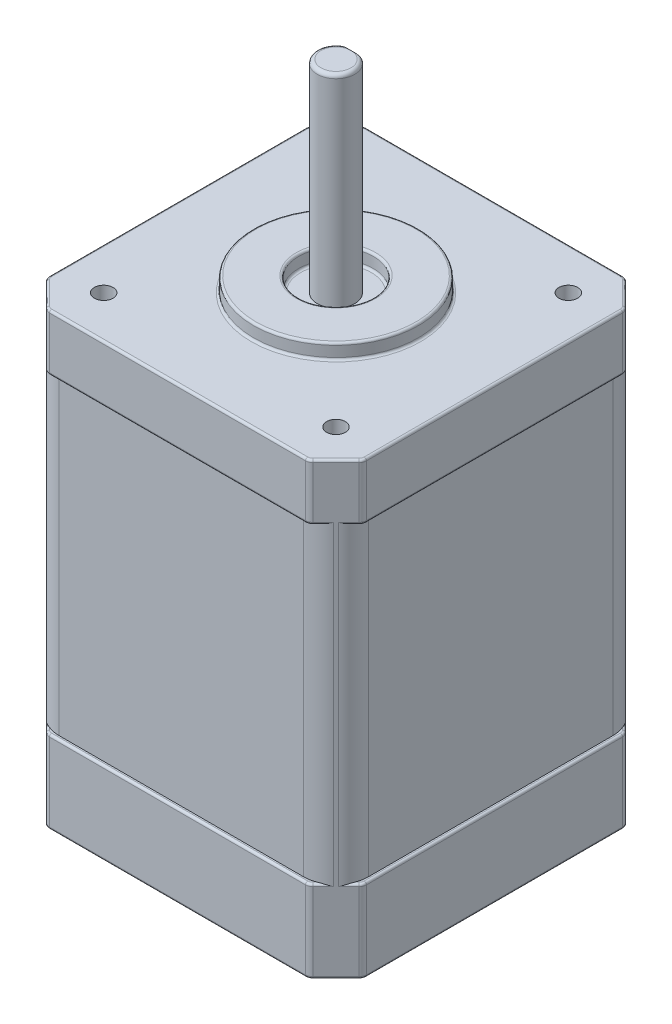
SolidWorks part; units mm, degrees
ref_plane "Front Plane" through (0, 0, 0) normal (0, 0, 1) x (1, 0, 0)
ref_plane "Top Plane" through (0, 0, 0) normal (0, 1, 0) x (1, 0, 0)
ref_plane "Right Plane" through (0, 0, 0) normal (1, 0, 0) x (0, 0, -1)
ref_plane "BottomMotorFacePlane" through (0, -60, 0) normal (0, 1, 0) x (1, 0, 0)
ref_plane "ProtrudngNubPlane" through (0, 2, 0) normal (0, 1, 0) x (1, 0, 0)
ref_plane "MotorShaftLimit" through (0, 27, 0) normal (0, 1, 0) x (1, 0, 0)
ref_plane "Front Cutout Plane" through (0, -7.5, 0) normal (0, 1, 0) x (1, 0, 0)
ref_plane "Rear Cutout Plane" through (0, -49, 0) normal (0, 1, 0) x (1, 0, 0)
ref_plane "JST Connnector Side Plane" through (-8, 0, 0) normal (1, 0, 0) x (0, 0, -1)
sketch "MasterLayoutSketch" plane through (0, 0, 0) normal (0, 1, 0) x (1, 0, 0)
  line L12 (-21.15, 21.15) -> (21.15, -21.15) construction
  line L13 (-21.15, 21.15) -> (21.15, 21.15) construction
  line L14 (-21.15, 21.15) -> (-21.15, -21.15) construction
  line L15 (-21.15, -21.15) -> (21.15, -21.15) construction
  line L17 (-21.15, -21.15) -> (21.15, 21.15) construction
  line L18 (21.15, 21.15) -> (21.15, -21.15) construction
  line L19 (-21.15, 17.5) -> (-21.15, -17.5)
  line L20 (-21.15, -17.5) -> (-17.5, -21.15)
  line L21 (-17.5, -21.15) -> (17.5, -21.15)
  line L22 (17.5, -21.15) -> (21.15, -17.5)
  line L23 (21.15, -17.5) -> (21.15, 17.5)
  line L24 (21.15, 17.5) -> (17.5, 21.15)
  line L25 (17.5, 21.15) -> (-17.5, 21.15)
  line L26 (-17.5, 21.15) -> (-21.15, 17.5)
  line L27 (-1.5, 2) -> (1.5, 2)
  line L28 (0, -2.5) -> (0, 2) construction
  circle A0 centre (0, 0) radius 11
  arc A1 (-1.5, 2) -> (1.5, 2) centre (0, 0) ccw
  point P8 (-15.5, 15.5)
  point P18 (15.5, 15.5)
  point P19 (15.5, -15.5)
  point P22 (-15.5, -15.5)
  dimension "D3" = 22
  dimension "D4" = 5
  dimension "D6" = 31
  dimension "D1" = 42.3
  dimension "D2" = 35
  dimension "D5" = 4.5
sketch "HolePositionSketch" plane through (0, 0, 0) normal (0, 1, 0) x (1, 0, 0)
  point P0 (-15.5, -15.5)
  point P2 (15.5, -15.5)
  point P4 (15.5, 15.5)
  point P6 (-15.5, 15.5)
sketch "MainBodySketch" plane through (0, 0, 0) normal (0, 1, 0) x (1, 0, 0)
  line L0 (21.15, 17.5) -> (17.5, 21.15) construction
  line L1 (21.15, -17.5) -> (21.15, 17.5) construction
  line L2 (17.5, -21.15) -> (21.15, -17.5) construction
  line L3 (-17.5, -21.15) -> (17.5, -21.15) construction
  line L4 (-21.15, -17.5) -> (-17.5, -21.15) construction
  line L5 (-21.15, 17.5) -> (-21.15, -17.5) construction
  line L6 (17.5, 21.15) -> (-17.5, 21.15) construction
  line L7 (-17.5, 21.15) -> (-21.15, 17.5) construction
  line L8 (21.15, 17.5) -> (17.5, 21.15)
  line L9 (21.15, -17.5) -> (21.15, 17.5)
  line L10 (17.5, -21.15) -> (21.15, -17.5)
  line L11 (-17.5, -21.15) -> (17.5, -21.15)
  line L12 (-21.15, -17.5) -> (-17.5, -21.15)
  line L13 (-21.15, 17.5) -> (-21.15, -17.5)
  line L14 (17.5, 21.15) -> (-17.5, 21.15)
  line L15 (-17.5, 21.15) -> (-21.15, 17.5)
extrude "MainMotorBody" add sketch "MainBodySketch" against normal up to surface (60 mm away) up to plane "BottomMotorFacePlane"
sketch "ProtrudingNubSketch" plane through (0, 0, 0) normal (0, 1, 0) x (1, 0, 0)
  circle A0 centre (0, 0) radius 11 construction
  circle A1 centre (0, 0) radius 11
  circle A2 centre (0, 0) radius 5
  dimension "D1" = 10
extrude "ProtrudingNub" add sketch "ProtrudingNubSketch" along normal up to surface (2 mm away) up to plane "ProtrudngNubPlane"
sketch "MotorShaftSketch" plane through (0, 0, 0) normal (0, 1, 0) x (1, 0, 0)
  line L0 (-1.5, 2) -> (1.5, 2) construction
  line L1 (-1.5, 2) -> (1.5, 2)
  arc A0 (-1.5, 2) -> (1.5, 2) centre (0, 0) ccw construction
  arc A1 (-1.5, 2) -> (1.5, 2) centre (0, 0) ccw
extrude "MotorShaft" add sketch "MotorShaftSketch" along normal up to surface (27 mm away) up to plane "MotorShaftLimit"
sketch "JST-PHConnectorSketch" plane through (0, -60, 0) normal (0, 1, 0) x (1, 0, 0)
  line L0 (17.5, 21.15) -> (-17.5, 21.15) construction
  line L1 (-8, 21.15) -> (8, 21.15)
  line L2 (-8, 21.15) -> (-8, 27.15)
  line L3 (-8, 27.15) -> (8, 27.15)
  line L4 (8, 21.15) -> (8, 27.15)
  line L5 (-8, 21.15) -> (8, 27.15) construction
  line L6 (-8, 27.15) -> (8, 21.15) construction
  point P0 (0, 24.15)
  dimension "D1" = 6
  dimension "D2" = 16
extrude "JST Connector" add sketch "JST-PHConnectorSketch" along normal blind 10.9
hole_wizard "M3MountingHoles" positions "Sketch8" profile "Sketch9" tap size "M3" standard "ISO"
sketch "Sketch8" plane through (0, 0, 0) normal (0, 1, 0) x (1, 0, 0)
  point P0 (-15.5, 15.5)
  point P3 (15.5, 15.5)
  point P6 (15.5, -15.5)
  point P9 (-15.5, -15.5)
sketch "Sketch9" plane through (-15.5, 0, -15.5) normal (1, 0, 0) x (0, 0, 1)
  line L0 (0, 0) -> (0, 6.7511)
  line L1 (0, 6.7511) -> (1.25, 6)
  line L2 (1.25, 6) -> (1.25, 0)
  line L5 (1.25, 0) -> (0, 0)
  line L10 (0, 6.7511) -> (-1.25, 6) construction
  line L11 (0, -6.35) -> (0, 107.95) construction
  dimension "Tap Drill Dia." = 2.5
  dimension "Tap Drill Depth" = 6
  dimension "Drill Angle" = 118
cosmetic thread "Hole Thread1" parameters "D1"=4.5, "D2"=3
cosmetic thread "Hole Thread2" parameters "D1"=4.5, "D2"=3
cosmetic thread "Hole Thread3" parameters "D1"=4.5, "D2"=3
cosmetic thread "Hole Thread4" parameters "D1"=4.5, "D2"=3
sketch "Cutout Sketch" plane through (0, -7.5, 0) normal (0, 1, 0) x (1, 0, 0)
  line L0 (21.15, 17.5) -> (17.5, 21.15) construction
  line L1 (17.5, 21.15) -> (-17.5, 21.15) construction
  line L2 (-17.5, 21.15) -> (-21.15, 17.5) construction
  line L3 (-21.15, 17.5) -> (-21.15, -17.5) construction
  line L4 (-21.15, -17.5) -> (-17.5, -21.15) construction
  line L5 (-17.5, -21.15) -> (17.5, -21.15) construction
  line L6 (17.5, -21.15) -> (21.15, -17.5) construction
  line L7 (21.15, -17.5) -> (21.15, 17.5) construction
  line L8 (21.15, 17.5) -> (20.65, 18)
  line L9 (17.5, 21.15) -> (-17.5, 21.15)
  line L10 (-17.5, 21.15) -> (-18, 20.65)
  line L11 (-21.15, 17.5) -> (-21.15, -17.5)
  line L12 (-21.15, -17.5) -> (-20.65, -18)
  line L13 (-17.5, -21.15) -> (17.5, -21.15)
  line L14 (17.5, -21.15) -> (18, -20.65)
  line L15 (21.15, -17.5) -> (21.15, 17.5)
  line L16 (-20.65, 18) -> (-20.65, -18)
  line L17 (-20.65, -20.65) -> (20.65, -20.65) construction
  line L18 (-20.65, -20.65) -> (-20.65, 20.65) construction
  line L19 (-20.65, 20.65) -> (20.65, 20.65) construction
  line L20 (20.65, -20.65) -> (20.65, 20.65) construction
  line L21 (-20.65, -20.65) -> (20.65, 20.65) construction
  line L22 (-20.65, 20.65) -> (20.65, -20.65) construction
  line L23 (-18, -20.65) -> (18, -20.65)
  line L24 (20.65, -18) -> (20.65, 18)
  line L25 (18, 20.65) -> (-18, 20.65)
  line L26 (-20.65, 18) -> (-21.15, 17.5)
  line L27 (18, 20.65) -> (17.5, 21.15)
  line L28 (20.65, -18) -> (21.15, -17.5)
  line L29 (-18, -20.65) -> (-17.5, -21.15)
  point P2 (0, 0)
  dimension "D1" = 0.5
extrude "Cutout" cut sketch "Cutout Sketch" against normal up to surface (41.5 mm away)
sketch "JST Connector Cutout" plane through (-8, 0, 0) normal (1, 0, 0) x (0, 0, -1)
  line L0 (27.15, -56) -> (21.15, -56)
  line L1 (21.15, -60) -> (27.15, -60) construction
  line L2 (21.15, -60) -> (27.15, -60) construction
  line L3 (21.15, -60) -> (21.15, -49) construction
  line L4 (21.15, -49) -> (27.15, -49) construction
  line L5 (27.15, -49) -> (27.15, -60) construction
  line L6 (21.15, -56) -> (21.15, -55.5)
  line L7 (21.15, -55.5) -> (27.15, -55.5)
  line L8 (27.15, -55.5) -> (27.15, -56)
  dimension "D1" = 11
  dimension "D2" = 0.5
  dimension "D3" = 4
extrude "JST Connector Split Cutout" cut sketch "JST Connector Cutout" along normal through all
fillet "Cosmetic Fillets" radius 4 8 edges at (18, -28.25, 20.65) (20.65, -28.25, 18) (-18, -28.25, 20.65) (-20.65, -28.25, 18) (-18, -28.25, -20.65) (-20.65, -28.25, -18) (18, -28.25, -20.65) (20.65, -28.25, -18)
fillet "Tiny Fillets" radius 1 16 edges at (-17.5, -3.75, -21.15) (-21.15, -3.75, -17.5) (-21.15, -3.75, 17.5) (-17.5, -3.75, 21.15) (17.5, -3.75, 21.15) (21.15, -3.75, 17.5) (21.15, -3.75, -17.5) (17.5, -3.75, -21.15) (17.5, -54.5, -21.15) (21.15, -54.5, -17.5) (21.15, -54.5, 17.5) (17.5, -54.5, 21.15) (-17.5, -54.5, 21.15) (-21.15, -54.5, 17.5) (-17.5, -54.5, -21.15) (-21.15, -54.5, -17.5)
fillet "Rear Block Fillets" radius 1 4 edges at (8, -58, -21.15) (-8, -58, -21.15) (8, -58, -27.15) (-8, -58, -27.15)
fillet "Nub Fillets" radius 0.3 4 edges at (0, 2, 11) (0, 0, 11) (0, 0, 5) (0, 2, 5)
fillet "Shaft Fillets" radius 0.5 3 edges at (0, 27, 2.5) (1.5, 13.5, -2) (-1.5, 13.5, -2)
fillet "Faceplate Fillets" radius 0.3 80 edges at (20.1678, -49, -18.4822) (21.0739, -49, -17.4685) (20.1678, -49, 18.4822) (21.0739, -49, 17.4685) (18.4822, -7.5, -20.1678) (17.4685, -7.5, -21.0739) (-18.4822, -7.5, -20.1678) (-17.4685, -7.5, -21.0739) (20.1678, -7.5, 18.4822) (21.0739, -7.5, 17.4685) (20.1678, -7.5, -18.4822) (21.0739, -7.5, -17.4685) (-18.4822, -7.5, 20.1678) (-17.4685, -7.5, 21.0739) (18.4822, -7.5, 20.1678) (17.4685, -7.5, 21.0739) (-20.1678, -7.5, -18.4822) (-21.0739, -7.5, -17.4685) (-20.1678, -7.5, 18.4822) (-21.0739, -7.5, 17.4685) (18.4822, -49, 20.1678) (17.4685, -49, 21.0739) (-18.4822, -49, 20.1678) (-17.4685, -49, 21.0739) (-20.1678, -49, 18.4822) (-21.0739, -49, 17.4685) (-20.1678, -49, -18.4822) (-21.0739, -49, -17.4685) (-18.4822, -49, -20.1678) (-17.4685, -49, -21.0739) (18.4822, -49, -20.1678) (17.4685, -49, -21.0739) (17.4685, 0, -21.0739) (19.325, 0, -19.325) (21.0739, 0, -17.4685) (21.15, 0, 0) (21.0739, 0, 17.4685) (19.325, 0, 19.325) (17.4685, 0, 21.0739) (0, 0, 21.15) (-17.4685, 0, 21.0739) (-19.325, 0, 19.325) (-21.0739, 0, 17.4685) (-21.15, 0, 0) (-21.0739, 0, -17.4685) (-19.325, 0, -19.325) (-17.4685, 0, -21.0739) (-17.4685, -60, -21.0739) (-19.325, -60, -19.325) (-21.0739, -60, -17.4685) (-21.15, -60, 0) (-21.0739, -60, 17.4685) (-19.325, -60, 19.325) (-17.4685, -60, 21.0739) (0, -60, 21.15) (17.4685, -60, 21.0739) (19.325, -60, 19.325) (21.0739, -60, 17.4685) (21.15, -60, 0) (21.0739, -60, -17.4685) (19.325, -60, -19.325) (17.4685, -60, -21.0739) (13.0429, -60, -21.15) (8.2929, -60, -21.4429) (8, -60, -24.15) (7.7071, -60, -26.8571) (0, -60, -27.15) (-7.7071, -60, -26.8571) (-8, -60, -24.15) (-8.2929, -60, -21.4429) (21.15, -49, 0) (0, -7.5, -21.15) (21.15, -7.5, 0) (0, -7.5, 21.15) (-21.15, -7.5, 0) (0, -49, 21.15) (-21.15, -49, 0) (0, -49, -21.15) (0, 0, -21.15) (-13.0429, -60, -21.15)
